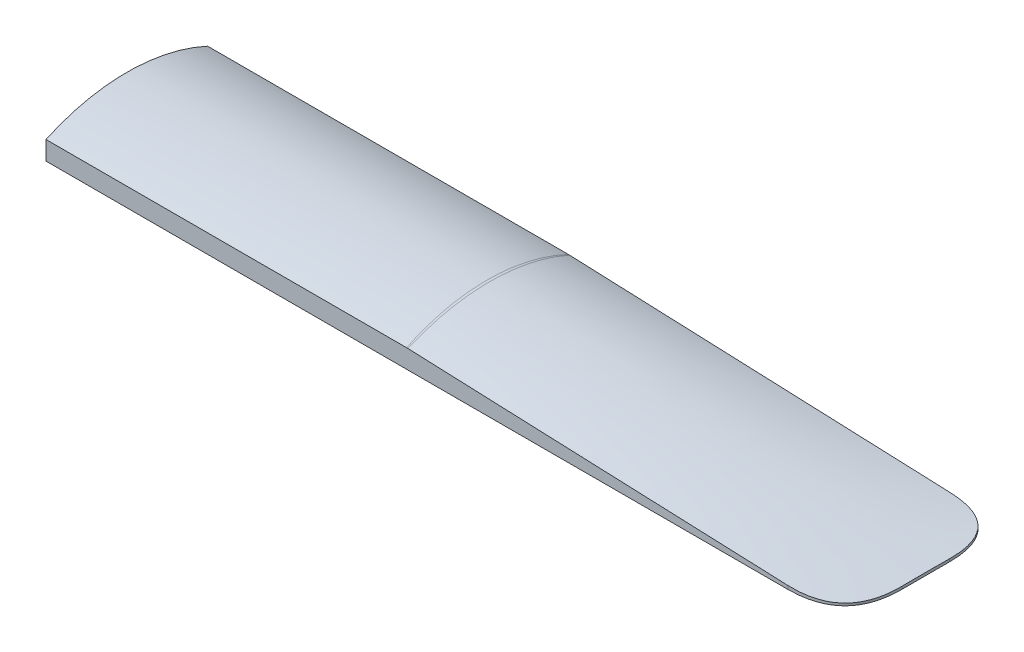
SolidWorks part; units mm, degrees
material "Balsa"
ref_plane "Front Plane" through (0, 0, 0) normal (0, 0, 1) x (1, 0, 0)
ref_plane "Top Plane" through (0, 0, 0) normal (0, 1, 0) x (1, 0, 0)
ref_plane "Right Plane" through (0, 0, 0) normal (1, 0, 0) x (0, 0, -1)
sketch "Sketch1" plane through (0, 0, 0) normal (1, 0, 0) x (0, 0, -1)
  line L0 (-14.17, 0) -> (0, 0)
  line L1 (7.7935, 0) -> (-7.7935, 0) construction
  line L2 (-7.085, 0) -> (-7.085, 3.2) construction
  line L3 (-14.17, 0) -> (-14.17, 1.64)
  line L4 (0, 0) -> (0, 1.64)
  arc A0 (-14.17, 1.64) -> (0, 1.64) centre (-7.085, -13.6689) cw
  point P10 (-7.085, 3.2)
  point P11 (-7.085, 3.2)
  dimension "D1" = 14.17
  dimension "D2" = 3.2
  dimension "D3" = 1.64
extrude "Boss-Extrude1" add sketch "Sketch1" along normal blind 31.67 contours A0 L4 L0 L3
ref_plane "Plane1" through (31.67, 0, 0) normal (1, 0, 0) x (0, 0, -1)
sketch "Sketch2" plane through (31.67, 0, 0) normal (1, 0, 0) x (0, 0, -1)
  line L4 (-14.17, 1.64) -> (-14.17, 0)
  line L5 (-14.17, 0) -> (0, 0)
  line L6 (0, 0) -> (0, 1.64)
  line L7 (-14.17, 1.64) -> (-14.17, 0)
  line L8 (-14.17, 0) -> (0, 0)
  line L9 (0, 0) -> (0, 1.64)
  arc A2 (0, 1.64) -> (-14.17, 1.64) centre (-7.085, -13.6689) ccw
  arc A3 (0, 1.64) -> (-14.17, 1.64) centre (-7.085, -13.6689) ccw
  dimension "D1" = 0
ref_plane "Plane2" through (70.02, 0, 0) normal (1, 0, 0) x (0, 0, -1)
sketch "Sketch4" plane through (70.02, 0, 0) normal (1, 0, 0) x (0, 0, -1)
  line L0 (-14.17, 0) -> (0, 0)
  line L1 (0, 0) -> (0, 0.1)
  line L2 (0, 0) -> (0, 1.64) construction
  line L4 (-14.17, 0) -> (-14.17, 0.1)
  line L5 (-14.17, 1.64) -> (-14.17, 0) construction
  arc A0 (-14.17, 0.1) -> (0, 0.1) centre (-7.085, -170.8413) cw
  dimension "D2" = 171.088
  dimension "D1" = 0.1
  dimension "D3" = 0.1
loft "Loft1" add profiles "Sketch2", "Sketch4" connector at (31.67, 1.64, 0) connector at (70.02, 0.1, 0)
fillet "Fillet1" radius 5 1 edges type face fillet first side face at (70.02, 0.05, 7.085) second side face at (48.346, 0.512, 0) conic rho 0.5
fillet "Fillet2" radius 5 1 edges type face fillet first side face at (40.676, 0.84, 14.17) second side face at (70.02, 0.0835, 9.585) conic rho 0.5
fillet "Fillet3" radius 3 1 edges type face fillet first side face at (55.57, 0.7249, 8.7517) second side face at (23.7525, 2.03, 8.8562) conic rho 0.5
sketch "Sketch6" plane through (0, 0, 0) normal (0, 0, 1) x (1, 0, 0)
  line L0 (27.8989, 4.7082) -> (-5.8842, -6.5528)
  line L1 (-5.8842, -6.5528) -> (-4.7378, 11.6536)
  line L2 (-4.7378, 11.6536) -> (27.8989, 4.7082)
extrude "Cut-Extrude3" [suppressed] cut sketch "Sketch6" against normal through all both and the other way through all
